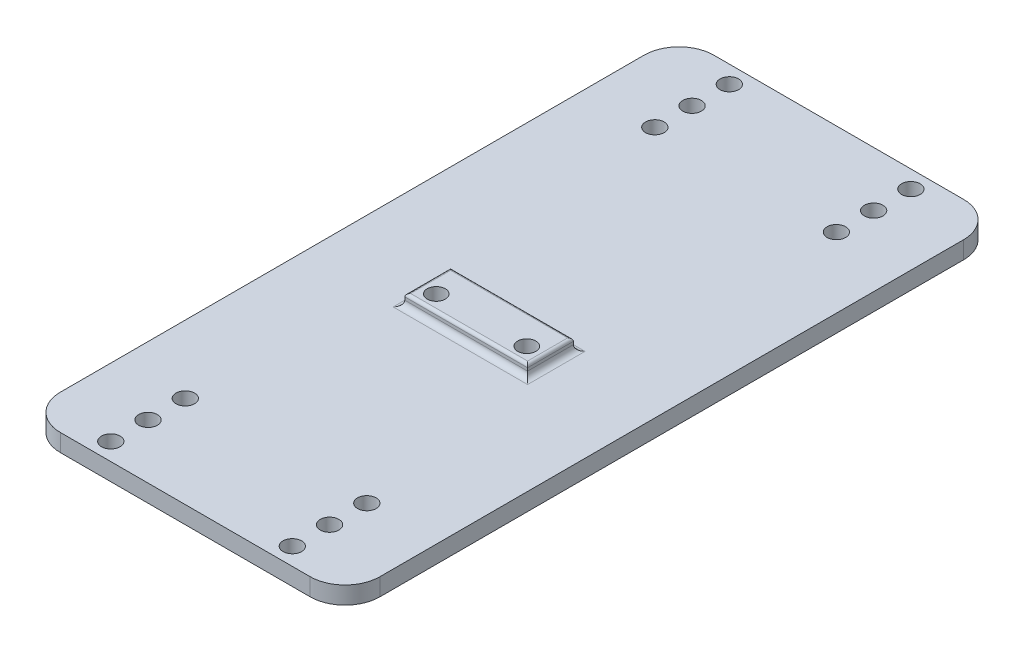
SolidWorks part; units mm, degrees
ref_plane "Front Plane" through (0, 0, 0) normal (0, 0, 1) x (1, 0, 0)
ref_plane "Top Plane" through (0, 0, 0) normal (0, 1, 0) x (1, 0, 0)
ref_plane "Right Plane" through (0, 0, 0) normal (1, 0, 0) x (0, 0, -1)
sketch "Sketch1" plane through (0, 0, 0) normal (0, 1, 0) x (1, 0, 0)
  line L0 (-92.2619, -19.1957) -> (-37.3377, -19.1957)
  line L1 (-37.3377, -19.1957) -> (-37.3377, 93.1143)
  line L2 (-37.3377, 36.9593) -> (-92.2619, 36.9593) construction
  line L3 (-92.2619, 93.1143) -> (-92.2619, -19.1957)
  line L4 (-92.2619, 93.1143) -> (-37.3377, 93.1143)
  circle A0 centre (-80.5998, -16.1917) radius 1.6
  circle A1 centre (-80.5998, -9.7917) radius 1.6
  circle A2 centre (-80.5998, -3.3917) radius 1.6
  circle A3 centre (-49.3998, -3.3917) radius 1.6
  circle A4 centre (-49.3998, -9.7917) radius 1.6
  circle A5 centre (-49.3998, -16.1917) radius 1.6
  circle A6 centre (-49.3998, 90.1102) radius 1.6
  circle A7 centre (-49.3998, 83.7102) radius 1.6
  circle A8 centre (-49.3998, 77.3102) radius 1.6
  circle A9 centre (-80.5998, 77.3102) radius 1.6
  circle A10 centre (-80.5998, 83.7102) radius 1.6
  circle A11 centre (-80.5998, 90.1102) radius 1.6
  dimension "D1" = 56.155
  dimension "D2" = 54.9243
  dimension "D3" = 11.6621
extrude "Boss-Extrude1" add sketch "Sketch1" along normal blind 3
fillet "Fillet1" radius 6 4 edges at (-92.2619, 1.5, -93.1143) (-37.3377, 1.5, -93.1143) (-92.2619, 1.5, 19.1957) (-37.3377, 1.5, 19.1957)
sketch "Sketch2" plane through (0, 3, 0) normal (0, 1, 0) x (1, 0, 0)
  line L0 (-92.2619, 36.9593) -> (-37.3377, 36.9593) construction
  line L1 (-92.2619, 87.1143) -> (-92.2619, -13.1957) construction
  line L2 (-37.3377, -13.1957) -> (-37.3377, 87.1143) construction
  line L3 (-64.7998, -19.1957) -> (-64.7998, 93.1143) construction
  line L4 (-86.2619, -19.1957) -> (-43.3377, -19.1957) construction
  line L5 (-43.3377, 93.1143) -> (-86.2619, 93.1143) construction
  line L6 (-75.3535, 29.0853) -> (-54.2461, 29.0853)
  line L7 (-75.3535, 29.0853) -> (-75.3535, 44.8333)
  line L8 (-75.3535, 44.8333) -> (-54.2461, 44.8333)
  line L9 (-54.2461, 29.0853) -> (-54.2461, 44.8333)
  line L10 (-75.3535, 29.0853) -> (-54.2461, 44.8333) construction
  line L11 (-75.3535, 44.8333) -> (-54.2461, 29.0853) construction
  line L12 (-75.3535, 36.9593) -> (-54.2461, 36.9593)
  circle A0 centre (-72.5786, 31.7205) radius 1.5558
  circle A1 centre (-57.0215, 31.7198) radius 1.5558
  point P12 (-64.7998, 36.9593)
  dimension "D3" = 3.1115
  dimension "D1" = 21.1074
  dimension "D2" = 15.748
  dimension "D4" = 2.6353
extrude "Boss-Extrude2" add sketch "Sketch2" along normal blind 2 contours L12 L7 L6 L9 A0 A1 region at (-64.7998, 3, -33.1534)
extrude "Cut-Extrude1" cut sketch "Sketch2<4>" against normal through all contours A0 | A1 region at (-72.5786, 3, -31.7205) region at (-57.0215, 3, -31.7198)
sketch "Sketch2<4>" plane through (0, 3, 0) normal (0, 1, 0) x (1, 0, 0) same geometry as "Sketch2"
fillet "Fillet2" radius 1 4 edges at (-75.3535, 3, -33.0223) (-64.7998, 3, -36.9593) (-64.7998, 3, -29.0853) (-54.2461, 3, -33.0223)
fillet "Fillet3" radius 0.5 4 edges at (-54.2461, 5, -33.0223) (-64.7998, 5, -36.9593) (-75.3535, 5, -33.0223) (-64.7998, 5, -29.0853)
